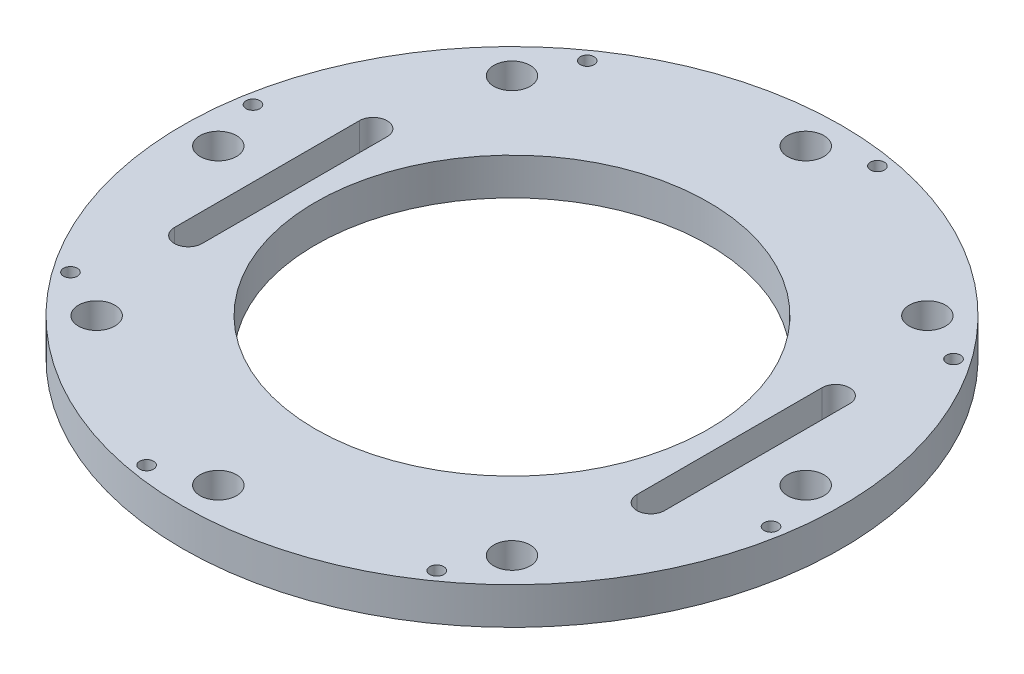
SolidWorks part; units mm, degrees
ref_plane "Front Plane" through (0, 0, 0) normal (0, 0, 1) x (1, 0, 0)
ref_plane "Top Plane" through (0, 0, 0) normal (0, 1, 0) x (1, 0, 0)
ref_plane "Right Plane" through (0, 0, 0) normal (1, 0, 0) x (0, 0, -1)
sketch "Sketch1" plane through (0, 0, 0) normal (0, 1, 0) x (1, 0, 0)
  line L0 (10, -4) -> (10, 4) construction
  line L1 (9.4, -4) -> (9.4, 4)
  line L2 (10.6, -4) -> (10.6, 4)
  line L3 (0, 0) -> (0, -14.25) construction
  line L4 (-10, -4) -> (-10, 4) construction
  line L5 (-9.4, -4) -> (-9.4, 4)
  line L6 (-10.6, -4) -> (-10.6, 4)
  line L7 (0, 0) -> (-13.1653, 5.4532) construction
  line L8 (0, 0) -> (-14.25, 0) construction
  circle A0 centre (0, 0) radius 14.25
  circle A1 centre (0, 0) radius 8.5
  arc A2 (9.4, -4) -> (10.6, -4) centre (10, -4) ccw
  arc A3 (10.6, 4) -> (9.4, 4) centre (10, 4) ccw
  arc A4 (-9.4, -4) -> (-10.6, -4) centre (-10, -4) cw
  arc A5 (-10.6, 4) -> (-9.4, 4) centre (-10, 4) cw
  circle A7 centre (-8.9803, -8.9803) radius 0.7874
  circle A8 centre (-12.7, 0) radius 0.7874
  circle A9 centre (-8.9803, 8.9803) radius 0.7874
  circle A10 centre (0, 12.7) radius 0.7874
  circle A11 centre (8.9803, 8.9803) radius 0.7874
  circle A12 centre (12.7, 0) radius 0.7874
  circle A13 centre (8.9803, -8.9803) radius 0.7874
  circle A14 centre (0, -12.7) radius 0.7874
  circle A15 centre (-13.5, 2.3) radius 0.3
  circle A17 centre (-7.9196, 11.1723) radius 0.3
  circle A18 centre (2.3, 13.5) radius 0.3
  circle A19 centre (11.1723, 7.9196) radius 0.3
  circle A20 centre (13.5, -2.3) radius 0.3
  circle A21 centre (7.9196, -11.1723) radius 0.3
  circle A22 centre (-2.3, -13.5) radius 0.3
  circle A23 centre (-11.1723, -7.9196) radius 0.3
  point P6 (10, 0)
  point P13 (-10, 0)
  point P38 (0, 0)
  point P44 (0, 0)
  point P58 (0, 0)
  point P61 (0, 0)
  dimension "D1" = 8
  dimension "D2" = 17
  dimension "D6" = 12.7
  dimension "D7" = 1.5748
  dimension "D12" = 0.6
  dimension "D3" = 1.2
  dimension "D4" = 8
  dimension "D5" = 10
  dimension "D8" = 12.7
  dimension "D9" = 8.9803
  dimension "D10" = 2.3
  dimension "D11" = 13.5
  dimension "D13" = 22.5
  dimension "D14" = 8
extrude "Boss-Extrude1" add sketch "Sketch1" along normal blind 1.6 contours A0 A3 L2 A2 L1 A1 L6 A5 L5 A4 region at (-13.8469, 0, 0)
ref_axis "Axis1" through (13.5, 1.6, 2.3) along (0, -1, 0)
ref_axis "Axis2" through (-13.5, 1.6, -2.3) along (0, -1, 0)
ref_plane "Plane1" through (0, 0, 0) normal (0.168, 0, -0.9858) x (-0.9858, 0, -0.168)
